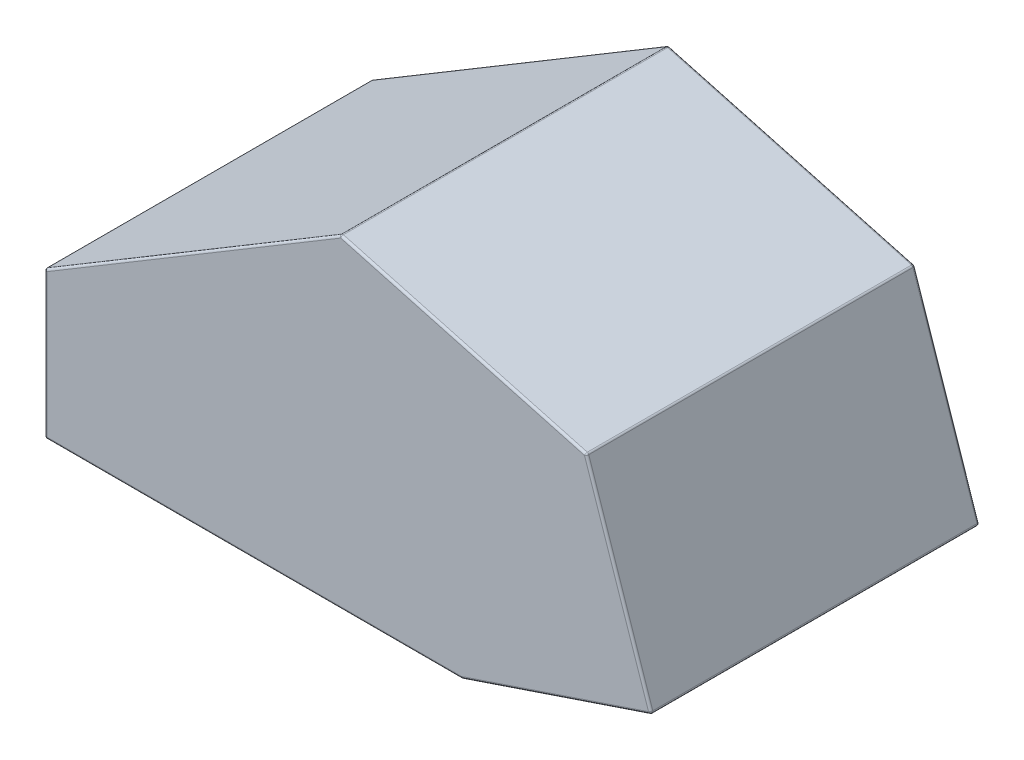
SolidWorks part; units mm, degrees
ref_plane "Front Plane" through (0, 0, 0) normal (0, 0, 1) x (1, 0, 0)
ref_plane "Top Plane" through (0, 0, 0) normal (0, 1, 0) x (1, 0, 0)
ref_plane "Right Plane" through (0, 0, 0) normal (1, 0, 0) x (0, 0, -1)
sketch "Sketch1" plane through (0, 0, 0) normal (0, 0, 1) x (1, 0, 0)
  line L0 (388.7933, 276.4638) -> (354.5115, 255.9287)
  line L1 (354.5115, 255.9287) -> (354.5115, 238.9239)
  line L2 (354.5115, 238.9239) -> (402.8969, 238.9239)
  line L3 (402.8969, 238.9239) -> (424.853, 246.3258)
  line L4 (424.853, 246.3258) -> (417.3086, 268.7047)
  line L5 (417.3086, 268.7047) -> (388.7933, 276.4638)
extrude "Boss-Extrude1" add sketch "Sketch1" along normal blind 19.05 and the other way blind 19.05 contours L5 L0 L1 L2 L3 L4
fillet "Fillet1" radius 0.254 18 edges at (421.0808, 257.5152, -19.05) (424.853, 246.3258, 0) (354.5115, 247.4263, -19.05) (354.5115, 238.9239, 0) (371.6524, 266.1963, -19.05) (354.5115, 255.9287, 0) (413.875, 242.6248, 19.05) (378.7042, 238.9239, 19.05) (354.5115, 247.4263, 19.05) (371.6524, 266.1963, 19.05) (403.051, 272.5843, 19.05) (421.0808, 257.5152, 19.05) (402.8969, 238.9239, 0) (378.7042, 238.9239, -19.05) (403.051, 272.5843, -19.05) (413.875, 242.6248, -19.05) (388.7933, 276.4638, 0) (417.3086, 268.7047, 0)
